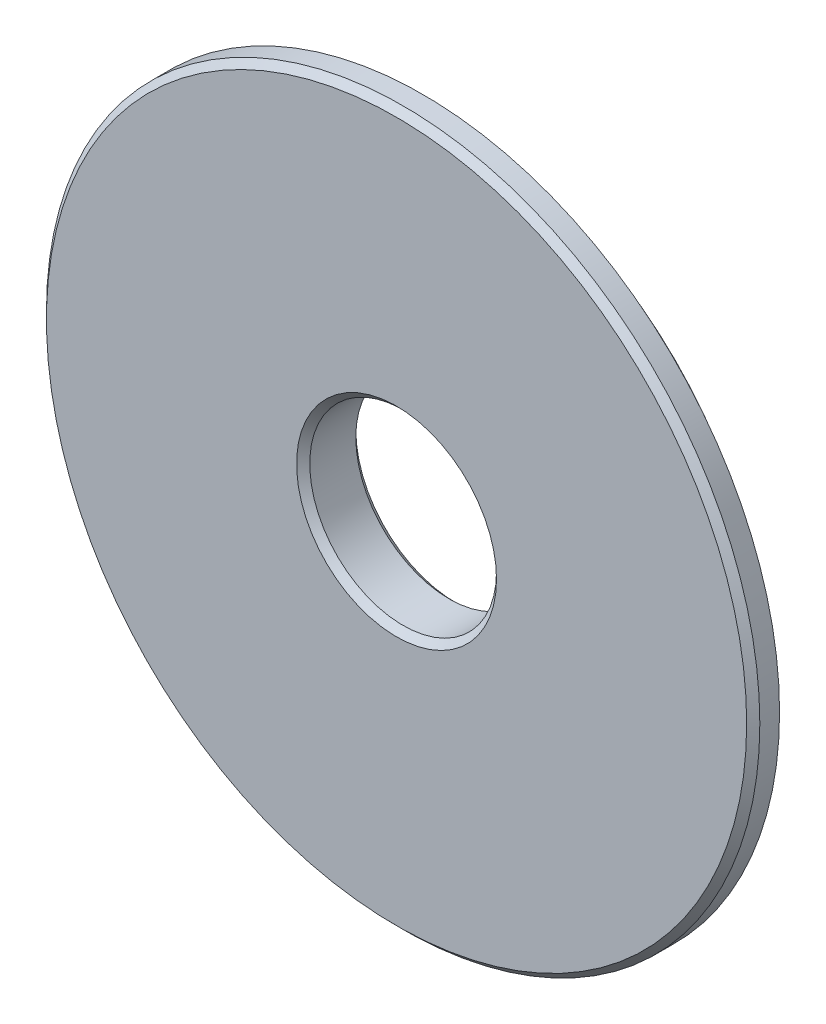
SolidWorks part; units mm, degrees
ref_plane "Front Plane" through (0, 0, 0) normal (0, 0, 1) x (1, 0, 0)
ref_plane "Top Plane" through (0, 0, 0) normal (0, 1, 0) x (1, 0, 0)
ref_plane "Right Plane" through (0, 0, 0) normal (1, 0, 0) x (0, 0, -1)
sketch "Sketch1" plane through (0, 0, 0) normal (0, 0, 1) x (1, 0, 0)
  circle A0 centre (0, 0) radius 24.12
  circle A1 centre (0, 0) radius 22.92
  dimension "D1" = 48.24
  dimension "D2" = 1.2
extrude "Boss-Extrude1" add sketch "Sketch1" along normal blind 2.5
sketch "Sketch2" plane through (0, 0, 2.5) normal (0, 0, 1) x (1, 0, 0)
  circle A0 centre (0, 0) radius 27.12
  circle A1 centre (0, 0) radius 24.12 construction
  dimension "D1" = 3
extrude "Boss-Extrude2" add sketch "Sketch2" along normal blind 2
sketch "Sketch3" plane through (0, 0, 4.5) normal (0, 0, 1) x (1, 0, 0)
  circle A0 centre (0, 0) radius 7.1
  dimension "D1" = 14.2
extrude "Cut-Extrude1" cut sketch "Sketch3" against normal through all
sketch "Sketch4" plane through (0, 0, 2.5) normal (0, 0, -1) x (-1, 0, 0)
  circle A0 centre (0, 0) radius 7.1
  circle A1 centre (0, 0) radius 8.3
  circle A2 centre (0, 0) radius 7.1 construction
  dimension "D1" = 1.2
extrude "Boss-Extrude3" add sketch "Sketch4" along normal through all
fillet "Fillet1" radius 2 2 edges at (22.92, 0, 2.5) (8.3, 0, 2.5)
chamfer "Chamfer1" distance 0.5 angle 45 4 edges at (27.12, 0, 4.5) (7.1, 0, 4.5) (-7.1, 0, 0) (24.12, 0, 0)
